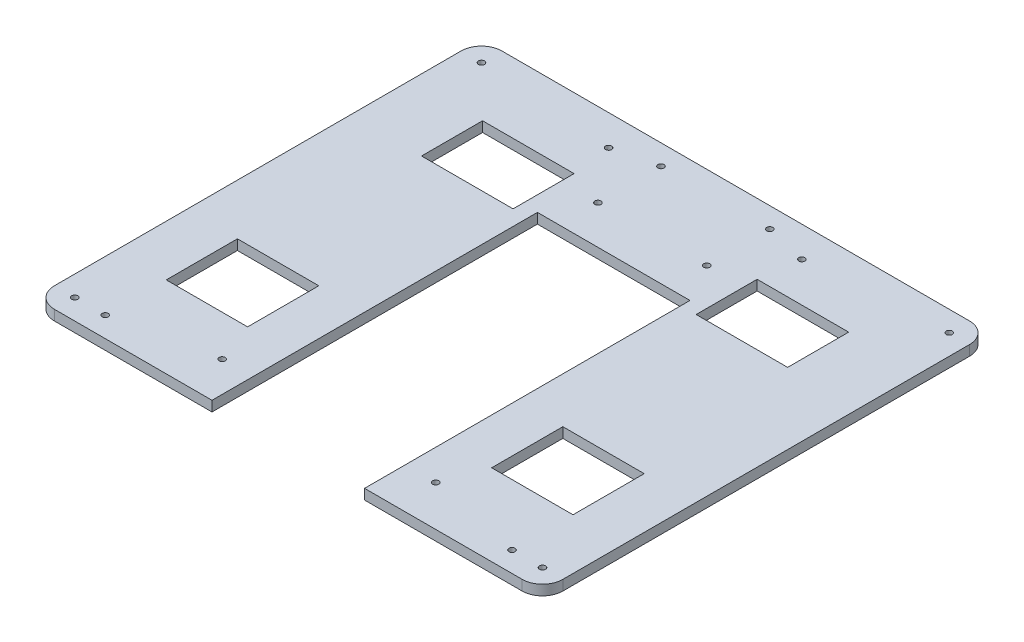
SolidWorks part; units mm, degrees
ref_plane "前视基准面" through (0, 0, 0) normal (0, 0, 1) x (1, 0, 0)
ref_plane "上视基准面" through (0, 0, 0) normal (0, 1, 0) x (1, 0, 0)
ref_plane "右视基准面" through (0, 0, 0) normal (1, 0, 0) x (0, 0, -1)
sketch "草图1" plane through (0, 0, 0) normal (0, 1, 0) x (1, 0, 0)
  line L1 (10, 0) -> (240, 0)
  line L2 (0, -10) -> (0, -210)
  line L3 (10, -220) -> (240, -220)
  line L4 (250, -10) -> (250, -210)
  arc A0 (0, -210) -> (10, -220) centre (10, -210) ccw
  arc A1 (240, -220) -> (250, -210) centre (240, -210) ccw
  arc A2 (240, 0) -> (250, -10) centre (240, -10) cw
  arc A3 (10, 0) -> (0, -10) centre (10, -10) ccw
  point P9 (250, -220)
  point P12 (250, 0)
  point P15 (0, 0)
  dimension "D3" = 10
  dimension "D1" = 250
  dimension "D2" = 220
extrude "凸台-拉伸1" add sketch "草图1" along normal blind 5
sketch "草图2" plane through (0, 0, 0) normal (0, -1, 0) x (1, 0, 0)
  line L0 (239.1778, 11.85) -> (239.1778, 76.15) construction
  line L1 (239.1778, 11.85) -> (239.1778, 76.15)
  line L2 (250, 210) -> (250, 10) construction
  line L3 (239.1778, 76.15) -> (250, 76.15)
  line L4 (239.1778, 76.15) -> (239.1778, 0)
  line L5 (239.1778, 0) -> (250, 0)
  line L6 (250, 76.15) -> (250, 0)
  line L7 (125, 220) -> (125, 0) construction
  line L8 (10, 220) -> (240, 220) construction
  line L9 (240, 0) -> (10, 0) construction
  line L10 (0, 76.15) -> (0, 0)
  line L11 (10.8222, 0) -> (0, 0)
  line L12 (10.8222, 76.15) -> (10.8222, 0)
  line L13 (10.8222, 76.15) -> (0, 76.15)
sketch "草图4" plane through (0, 0, 0) normal (0, -1, 0) x (1, 0, 0)
  line L1 (125, 0) -> (125, 220) construction
  line L2 (240, 0) -> (10, 0) construction
  line L3 (10, 220) -> (240, 220) construction
  line L8 (170, 64.475) -> (170, 34.475)
  line L16 (215, 34.475) -> (170, 34.475)
  line L17 (215, 64.475) -> (215, 34.475)
  line L18 (215, 64.475) -> (170, 64.475)
  line L19 (209.9, 64.475) -> (215, 64.475)
  line L20 (215, 64.475) -> (215, 46.825)
  line L21 (204.1, 64.475) -> (199, 64.475)
  line L22 (209.9, 64.475) -> (215, 64.475)
  line L23 (204.1, 64.475) -> (199, 64.475)
  line L24 (40.1, 64.475) -> (45.9, 64.475)
  line L25 (35, 64.475) -> (35, 46.825)
  line L26 (45.9, 64.475) -> (51, 64.475)
  line L27 (215, 64.475) -> (215, 46.825)
  line L28 (209.9, 64.475) -> (204.1, 64.475)
  line L29 (0, 10) -> (0, 210) construction
  line L30 (40.1, 64.475) -> (35, 64.475)
  line L31 (45.9, 64.475) -> (51, 64.475)
  line L33 (35, 64.475) -> (35, 46.825)
  line L35 (40.1, 64.475) -> (35, 64.475)
  line L38 (35, 64.475) -> (80, 64.475)
  line L39 (35, 64.475) -> (35, 34.475)
  line L120 (35, 34.475) -> (80, 34.475)
  line L121 (80, 64.475) -> (80, 34.475)
  dimension "D3" = 45
  dimension "D4" = 30
  dimension "D1" = 35
extrude "切除-拉伸3" cut sketch "草图4" against normal blind 5 contours L24 L30 L25 L26 | L18 L8 L16 L17 region at (57.5, 0, 49.475)
sketch "草图5" plane through (0, 0, 0) normal (0, -1, 0) x (1, 0, 0)
  line L0 (125, 220) -> (125, 0) construction
  line L1 (10, 220) -> (240, 220) construction
  line L2 (240, 0) -> (10, 0) construction
  line L3 (87.5, 220) -> (162.5, 220) construction
  line L4 (87.5, 220) -> (87.5, 60)
  line L5 (162.5, 220) -> (87.5, 220)
  line L6 (162.5, 220) -> (162.5, 60)
  line L7 (162.5, 60) -> (87.5, 60)
  point P11 (125, 60)
  dimension "D1" = 37.5
  dimension "D2" = 160
extrude "切除-拉伸4" cut sketch "草图5" against normal blind 5
sketch "草图6" plane through (0, 0, 0) normal (0, -1, 0) x (1, 0, 0)
  line L0 (72.5, 220) -> (72.5, 200) construction
  line L1 (10, 220) -> (87.5, 220) construction
  line L2 (72.5, 200) -> (87.5, 200) construction
  line L7 (87.5, 220) -> (87.5, 60) construction
  line L8 (125, 60) -> (125, 181.8158) construction
  line L9 (87.5, 60) -> (162.5, 60) construction
  line L10 (87.5, 60) -> (87.5, 0) construction
  line L11 (240, 0) -> (10, 0) construction
  line L12 (87.5, 20) -> (92.5, 20) construction
  line L13 (92.5, 20) -> (92.5, 0) construction
  line L14 (92.5, 20) -> (107.5, 20) construction
  circle A0 centre (72.5, 200) radius 1.5
  circle A3 centre (177.5, 200) radius 1.5
  dimension "D3" = 3
  dimension "D1" = 20
  dimension "D2" = 15
  dimension "D4" = 5
  dimension "D5" = 20
  dimension "D6" = 15
extrude "切除-拉伸5" cut sketch "草图6" against normal up to next contours A0 | A3
sketch "草图7" plane through (0, 0, 0) normal (0, -1, 0) x (1, 0, 0)
  line L0 (17, 15) -> (17, 73) construction
  line L1 (25, 29) -> (25, 59) construction
  line L2 (17, 44) -> (25, 44) construction
  line L3 (240, 0) -> (10, 0) construction
  line L5 (125, 60) -> (125, 0) construction
  line L6 (87.5, 60) -> (162.5, 60) construction
  line L8 (233, 44) -> (225, 44) construction
  line L9 (225, 29) -> (225, 59) construction
  line L10 (233, 15) -> (233, 73) construction
  line L11 (0, 10) -> (0, 210) construction
  circle A0 centre (17, 15) radius 1.6
  circle A1 centre (25, 29) radius 1.6
  circle A2 centre (25, 59) radius 1.6
  circle A3 centre (17, 73) radius 1.6
  circle A4 centre (233, 73) radius 1.6
  circle A5 centre (225, 59) radius 1.6
  circle A6 centre (225, 29) radius 1.6
  circle A7 centre (233, 15) radius 1.6
  dimension "D1" = 8
  dimension "D2" = 58
  dimension "D3" = 30
  dimension "D4" = 58
  dimension "D5" = 17
  dimension "D6" = 15
sketch "草图8" plane through (0, 0, 0) normal (0, -1, 0) x (1, 0, 0)
  line L0 (250, 170) -> (235, 170) construction
  line L1 (250, 210) -> (250, 10) construction
  line L2 (235, 170) -> (235, 220) construction
  line L3 (162.5, 220) -> (240, 220) construction
  line L4 (235, 170) -> (235, 100) construction
  line L5 (235, 100) -> (250, 100) construction
  line L6 (125, 60) -> (125, 122.441) construction
  line L7 (87.5, 60) -> (162.5, 60) construction
  line L8 (15, 170) -> (15, 100) construction
  circle A0 centre (235, 170) radius 1.5
  circle A1 centre (235, 100) radius 1.5
  circle A2 centre (15, 100) radius 1.5
  circle A3 centre (15, 170) radius 1.5
  dimension "D4" = 3
  dimension "D5" = 3
  dimension "D1" = 15
  dimension "D2" = 50
  dimension "D3" = 70
sketch "草图9" plane through (0, 0, 0) normal (0, -1, 0) x (1, 0, 0)
  line L0 (87.5, 60) -> (87.5, 0) construction
  line L1 (240, 0) -> (10, 0) construction
  line L2 (87.5, 0) -> (87.5, 15) construction
  line L3 (87.5, 15) -> (77.5, 15) construction
  line L4 (10, 220) -> (10, 210) construction
  line L5 (125, 60) -> (125, 0) construction
  line L6 (87.5, 60) -> (162.5, 60) construction
  circle A0 centre (77.5, 15) radius 1.5
  circle A1 centre (10, 210) radius 1.5
  circle A2 centre (240, 210) radius 1.5
  circle A3 centre (172.5, 15) radius 1.5
  dimension "D3" = 3
  dimension "D4" = 3
  dimension "D1" = 15
  dimension "D2" = 10
extrude "切除-拉伸9" cut sketch "草图9" against normal up to next
sketch "草图10" plane through (0, 0, 0) normal (0, -1, 0) x (1, 0, 0)
  line L0 (125, 60) -> (125, 0) construction
  line L1 (0, 0) -> (8, 0)
  line L2 (0, 0) -> (0, 85)
  line L3 (0, 85) -> (8, 85)
  line L4 (8, 0) -> (8, 85)
  line L5 (87.5, 60) -> (162.5, 60) construction
  line L6 (240, 0) -> (10, 0) construction
  line L7 (242, 0) -> (242, 85)
  line L8 (250, 85) -> (242, 85)
  line L9 (250, 0) -> (250, 85)
  line L10 (250, 0) -> (242, 0)
  dimension "D1" = 8
  dimension "D2" = 85
sketch "草图11" plane through (0, 0, 0) normal (0, -1, 0) x (1, 0, 0)
  line L0 (10, 210) -> (25, 210) construction
  line L1 (125, 60) -> (125, 101.9448) construction
  line L2 (87.5, 60) -> (162.5, 60) construction
  circle A0 centre (25, 210) radius 1.5
  circle A1 centre (225, 210) radius 1.5
  dimension "D2" = 3
  dimension "D1" = 15
extrude "切除-拉伸10" cut sketch "草图11" against normal blind 10
sketch "草图12" plane through (0, 0, 0) normal (0, -1, 0) x (1, 0, 0)
  line L0 (10, 0) -> (10, 10) construction
  line L1 (125, 60) -> (125, 0) construction
  line L2 (87.5, 60) -> (162.5, 60) construction
  line L3 (240, 0) -> (10, 0) construction
  circle A0 centre (10, 10) radius 1.5
  circle A1 centre (240, 10) radius 1.5
  dimension "D1" = 3
extrude "切除-拉伸11" cut sketch "草图12" against normal blind 10
sketch "草图13" plane through (0, 0, 0) normal (0, -1, 0) x (1, 0, 0)
  line L0 (125, 60) -> (125, 0) construction
  line L1 (87.5, 60) -> (162.5, 60) construction
  line L2 (240, 0) -> (10, 0) construction
  line L4 (98.25, 10) -> (151.75, 10) construction
  line L5 (98.25, 10) -> (98.25, 41) construction
  line L6 (98.25, 41) -> (151.75, 41) construction
  line L7 (151.75, 10) -> (151.75, 41) construction
  line L8 (98.25, 10) -> (151.75, 41) construction
  line L9 (98.25, 41) -> (151.75, 10) construction
  circle A0 centre (98.25, 10) radius 1.5
  circle A1 centre (98.25, 41) radius 1.5
  circle A2 centre (151.75, 41) radius 1.5
  circle A3 centre (151.75, 10) radius 1.5
  point P6 (125, 25.5)
  dimension "D4" = 3
  dimension "D5" = 3
  dimension "D6" = 3
  dimension "D7" = 3
  dimension "D1" = 31
  dimension "D2" = 53.5
  dimension "D3" = 10
extrude "切除-拉伸12" cut sketch "草图13" against normal blind 10
sketch "草图14" plane through (0, 0, 0) normal (0, -1, 0) x (1, 0, 0)
  line L0 (0, 10) -> (0, 210) construction
  line L1 (65, 180) -> (25, 180)
  line L2 (65, 180) -> (65, 145)
  line L3 (65, 145) -> (25, 145)
  line L4 (25, 180) -> (25, 145)
  line L5 (10, 220) -> (87.5, 220) construction
  line L6 (125, 60) -> (125, 106.4856) construction
  line L7 (87.5, 60) -> (162.5, 60) construction
  line L8 (225, 180) -> (225, 145)
  line L9 (185, 145) -> (225, 145)
  line L10 (185, 180) -> (185, 145)
  line L11 (185, 180) -> (225, 180)
  dimension "D1" = 35
  dimension "D2" = 40
  dimension "D3" = 25
  dimension "D4" = 40
extrude "切除-拉伸13" cut sketch "草图14" against normal blind 10
